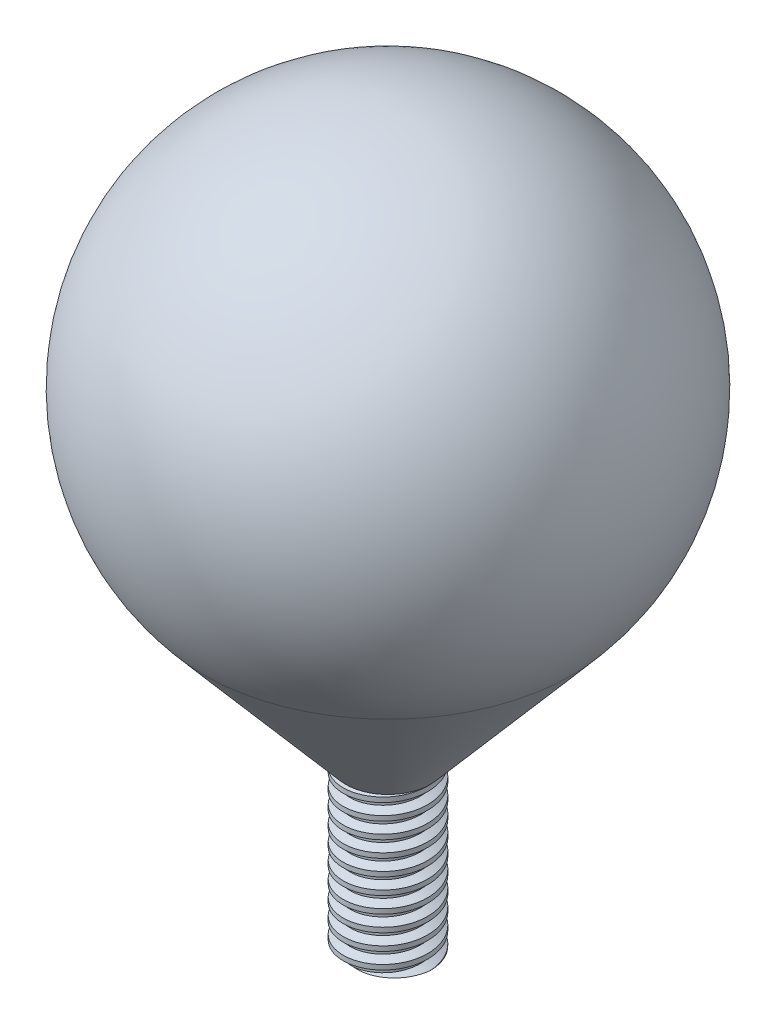
SolidWorks part; units mm, degrees
ref_plane "Front Plane" through (0, 0, 0) normal (0, 0, 1) x (1, 0, 0)
ref_plane "Top Plane" through (0, 0, 0) normal (0, 1, 0) x (1, 0, 0)
ref_plane "Right Plane" through (0, 0, 0) normal (1, 0, 0) x (0, 0, -1)
sketch "Sketch1" plane through (0, 0, 0) normal (0, 0, 1) x (1, 0, 0)
  line L0 (0, -260.4644) -> (0, 12762.7567) construction
  line L1 (-2.625, -20) -> (-2.625, -30)
  line L2 (-2.625, -30) -> (0, -30)
  line L5 (-2.625, -20) -> (-11.3953, -9.7544)
  line L6 (0, 15) -> (0, -30)
  arc A0 (0, 15) -> (-11.3953, -9.7544) centre (0, 0) ccw
  dimension "D3" = 15
  dimension "D1" = 10
  dimension "D2" = 2.625
  dimension "D4" = 30
revolve "Revolve1" add sketch "Sketch1" angle 360 about L0
thread "Thread2" pitch 0.8 method cut profile "Thread Profile2" start angle 0, offset 1, length 0, pitch 1, diameter 5.25
ref_plane "Plane2" through (2.625, -31, 0) normal (0, 0, 1) x (1, 0, 0)
sketch "Thread Profile2" plane through (2.625, -31, 0) normal (0, 0, 1) x (1, 0, 0)
  line L0 (0, 0) -> (0, 0.8) construction
  line L11 (0, 0) -> (0, 0.7)
  line L12 (0, 0.7) -> (-0.433, 0.45)
  line L13 (-0.433, 0.45) -> (-0.433, 0.25)
  line L15 (-0.433, 0.25) -> (0, 0)
  line L17 (-0.433, 0.35) -> (0, 0.35) construction
  point P2 (0, 0)
  dimension "Pitch" = 0.8
  dimension "Profile_Angle" = 60
  dimension "Profile_Land" = 0.2
  dimension "Profile_Height" = 0.433
